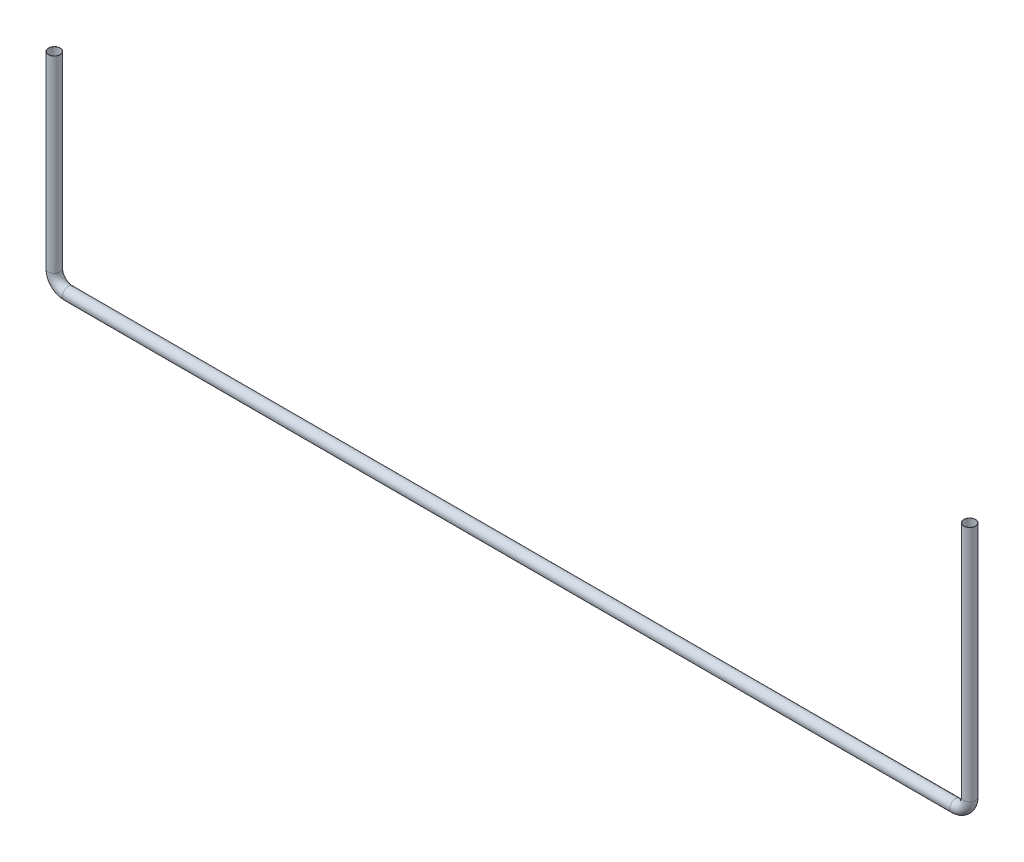
SolidWorks part; units mm, degrees
ref_plane "Plano frontal" through (0, 0, 0) normal (0, 0, 1) x (1, 0, 0)
ref_plane "Plano superior" through (0, 0, 0) normal (0, 1, 0) x (1, 0, 0)
ref_plane "Plano direito" through (0, 0, 0) normal (1, 0, 0) x (0, 0, -1)
sketch3d "3DSketch1"
  line L0 (-38227.539, -16797.9151, 42621.7002) -> (-38227.539, -16467.0514, 42621.7002) construction
  line L1 (-38227.539, -16772.4516, 42621.7002) -> (-38227.539, -16797.9151, 42621.7002) construction
  line L2 (-38227.539, -16467.0514, 42621.7002) -> (-38227.539, -17268.4637, 42621.7002)
  line L3 (-38167.539, -17328.4637, 42621.7002) -> (-34389.4008, -17328.4637, 42621.7002)
  line L4 (-34329.4008, -17268.4637, 42621.7002) -> (-34329.4008, -16256.6264, 42621.7002)
  line L5 (-34355.3293, -16256.7026, 42621.7037) -> (-34242.064, -16256.7026, 42621.7037) construction
  arc A0 (-34389.4008, -17328.4637, 42621.7002) -> (-34329.4008, -17268.4637, 42621.7002) centre (-34389.4008, -17268.4637, 42621.7002) ccw
  arc A3 (-38167.539, -17328.4637, 42621.7002) -> (-38227.539, -17268.4637, 42621.7002) centre (-38167.539, -17268.4637, 42621.7002) ccw
  point P5 (0, 0, 0)
  point P6 (-34250.2846, -16264.6737, 42621.7002)
  point P9 (-34330.3293, -16256.7026, 42621.7037)
  point P16 (-38227.539, -17328.4637, 42621.7002)
  point P17 (-38167.539, -17268.4637, 42561.7002)
  point P18 (-34329.4008, -17328.4637, 42621.7002)
  point P19 (-34389.4008, -17268.4637, 42681.7002)
  dimension "D1" = 60
sweep "Sweep-Thin1" add path "3DSketch1" circular profile diameter 50 parameters "D1"=1, "D3"=50
